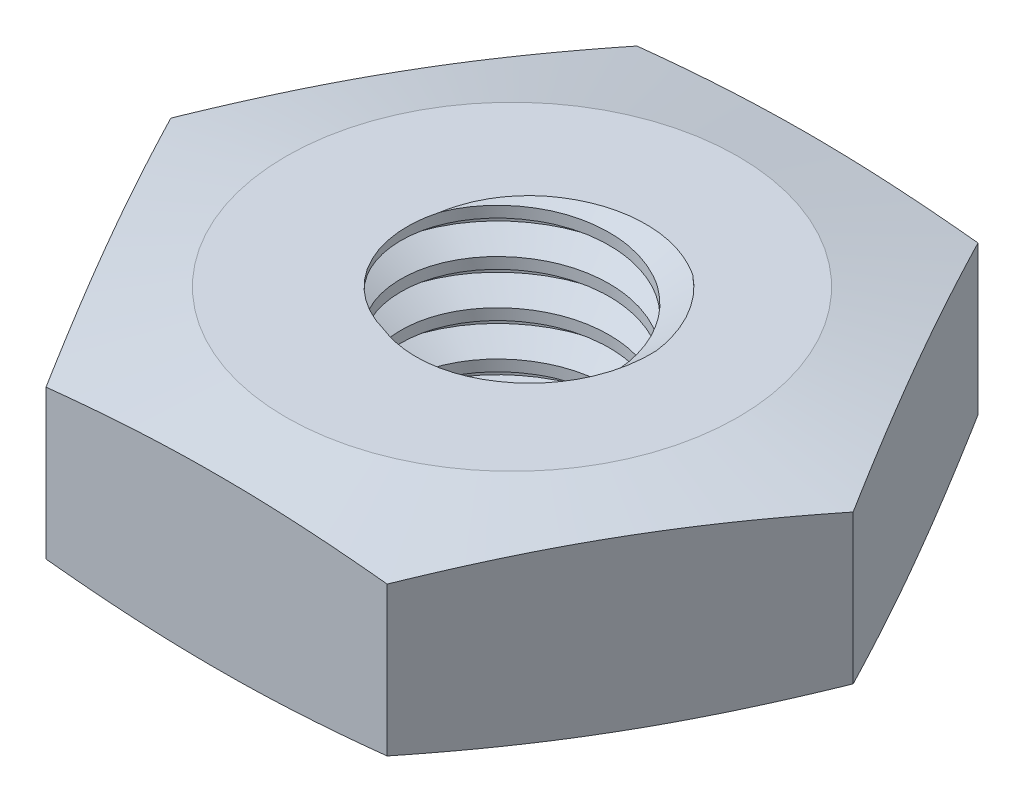
SolidWorks part; units mm, degrees
ref_plane "Front Plane" through (0, 0, 0) normal (0, 0, 1) x (1, 0, 0)
ref_plane "Top Plane" through (0, 0, 0) normal (0, 1, 0) x (1, 0, 0)
ref_plane "Right Plane" through (0, 0, 0) normal (1, 0, 0) x (0, 0, -1)
sketch "Sketch1" plane through (0, 0, 0) normal (0, 1, 0) x (1, 0, 0)
  line L1 (-2.6905, -4.66) -> (2.6905, -4.66)
  line L2 (2.6905, -4.66) -> (5.3809, 0)
  line L3 (5.3809, 0) -> (2.6905, 4.66)
  line L4 (2.6905, 4.66) -> (-2.6905, 4.66)
  line L5 (-2.6905, 4.66) -> (-5.3809, 0)
  line L6 (-5.3809, 0) -> (-2.6905, -4.66)
  circle A0 centre (0, 0) radius 4.66 construction
  dimension "D1" = 9.32
extrude "Boss-Extrude1" add sketch "Sketch1" along normal mid plane 3.12
hole_wizard "M4x0.7 Tapped Hole1" positions "Sketch2" profile "Sketch3" tap size "M4x0.7" standard "ANSI Metric"
sketch "Sketch2" plane through (0, -1.56, 0) normal (0, -1, 0) x (-1, 0, 0)
  point P0 (0, 0)
cosmetic thread "Hole Thread1" parameters "D1"=8, "D2"=4
sketch "Sketch3" plane through (0, -1.56, 0) normal (1, 0, 0) x (0, 0, -1)
  line L0 (0, 0) -> (0, 8.5914)
  line L1 (0, 8.5914) -> (1.65, 7.6)
  line L2 (1.65, 7.6) -> (1.65, 0)
  line L5 (1.65, 0) -> (0, 0)
  line L10 (0, 8.5914) -> (-1.65, 7.6) construction
  line L11 (0, -6.35) -> (0, 107.95) construction
  dimension "Tap Drill Dia." = 3.3
  dimension "Tap Drill Depth" = 7.6
  dimension "Drill Angle" = 118
thread "Thread1" pitch 0.7 method cut profile "Thread Profile1" start angle 0, offset 0, length 10, pitch 0.7, diameter 3.3
ref_plane "Plane1" through (1.65, -1.56, 0) normal (0, 0, 1) x (1, 0, 0)
sketch "Thread Profile1" plane through (1.65, -1.56, 0) normal (0, 0, 1) x (1, 0, 0)
  line L0 (0, 0) -> (0, 0.7) construction
  line L1 (0, 0) -> (0.3789, 0.2187)
  line L2 (0.3789, 0.2187) -> (0.3789, 0.3062)
  line L3 (0.3789, 0.3062) -> (0, 0.525)
  line L4 (0.3789, 0.2625) -> (0, 0.2625) construction
  line L11 (0, 0) -> (0, 0.525)
  point P2 (0, 0)
  dimension "Pitch" = 0.7
  dimension "Profile_Angle" = 60
  dimension "Profile_Land" = 0.0875
  dimension "Profile_Height" = 0.3789
sketch "Sketch6" plane through (0, 0, 0) normal (0, 0, 1) x (1, 0, 0)
  line L0 (2.0051, 1.56) -> (3.5651, 1.56) construction
  line L1 (-2.6905, 1.56) -> (2.6905, 1.56) construction
  line L2 (2.013, 1.56) -> (-0.4243, 1.56) construction
  line L3 (3.5651, 1.56) -> (5.3809, 1.56)
  line L4 (5.3809, 1.56) -> (5.3809, 1.174)
  line L5 (5.3809, 1.56) -> (5.3809, -1.56) construction
  line L6 (5.3809, 1.174) -> (3.5651, 1.56)
  line L7 (0, 0) -> (0, 1.56) construction
  dimension "D1" = 1.56
  dimension "D2" = 12
revolve "Cut-Revolve1" cut sketch "Sketch6" angle 360 about L7
mirror "Mirror1" about plane through (0, 0, 0) normal (0, 1, 0) of "Cut-Revolve1"
